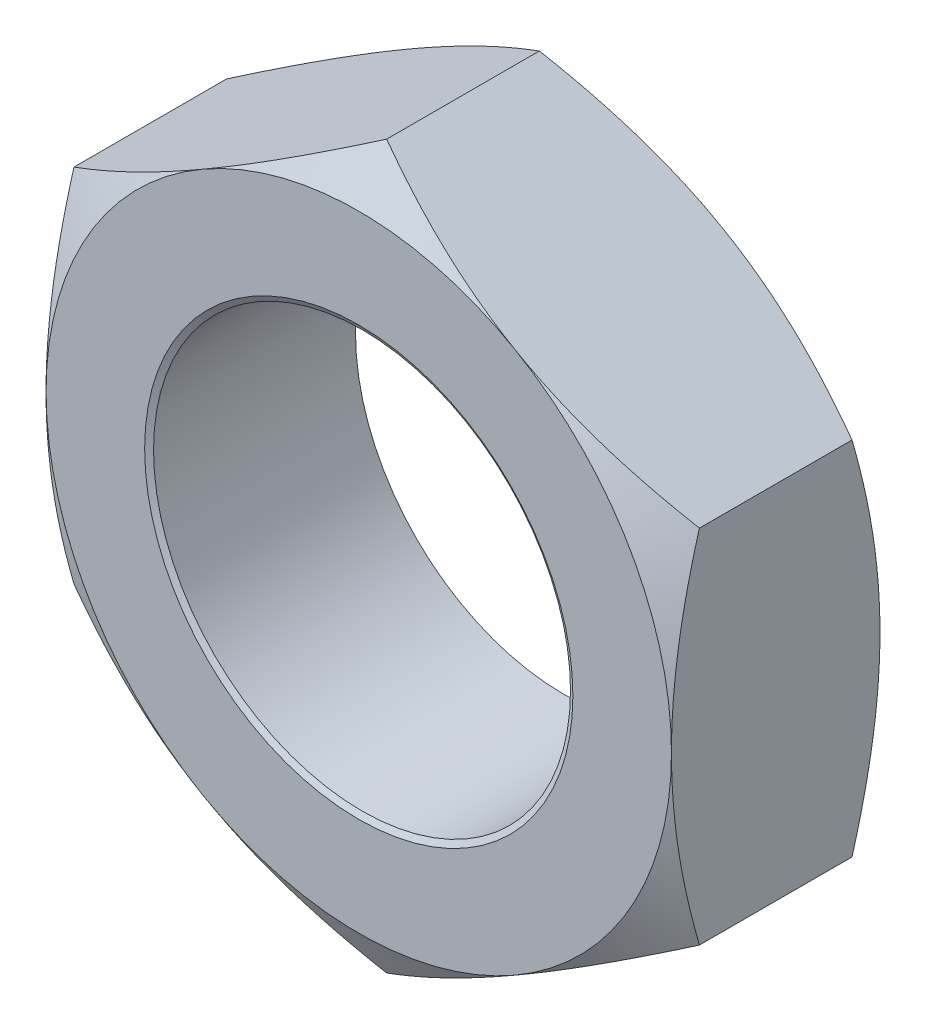
SolidWorks part; units mm, degrees
ref_plane "Front Plane" through (0, 0, 0) normal (0, 0, 1) x (1, 0, 0)
ref_plane "Top Plane" through (0, 0, 0) normal (0, 1, 0) x (1, 0, 0)
ref_plane "Right Plane" through (0, 0, 0) normal (1, 0, 0) x (0, 0, -1)
sketch "Sketch1" plane through (0, 0, 0) normal (0, 0, 1) x (1, 0, 0)
  line L1 (0, 13.8564) -> (-12, 6.9282)
  line L2 (-12, 6.9282) -> (-12, -6.9282)
  line L3 (-12, -6.9282) -> (0, -13.8564)
  line L4 (0, -13.8564) -> (12, -6.9282)
  line L5 (12, -6.9282) -> (12, 6.9282)
  line L6 (12, 6.9282) -> (0, 13.8564)
  circle A0 centre (0, 0) radius 12 construction
  circle A1 centre (0, 0) radius 8
  point P1 (0, 8)
  point P11 (8, 0)
  dimension "Thread Size" = 16
  dimension "HexWIdth" = 24
sketch "Sketch2" plane through (0, 0, 0) normal (1, 0, 0) x (0, 0, -1)
  line L0 (4, 0) -> (-4, 0) construction
  line L1 (-4, -8) -> (-4, 8) construction
  line L8 (-5.875, 8.2165) -> (-3.875, 8.2165) construction
  line L9 (-3.875, 8.2165) -> (-4.875, 6.4845) construction
  line L10 (-4.875, 6.4845) -> (-5.875, 8.2165) construction
  line L11 (-5.75, 8) -> (-4, 8) construction
  line L12 (-5, 6.701) -> (-4.75, 6.701) construction
  line L13 (-4.875, 6.4845) -> (-4.875, 6.701) construction
  line L14 (-4.875, 8) -> (-4.875, 8.2165) construction
  line L15 (-5.8125, 8.1083) -> (-3.9375, 8.1083)
  line L16 (-3.9375, 8.1083) -> (-4.75, 6.701)
  line L17 (-4.75, 6.701) -> (-5, 6.701)
  line L18 (-5, 6.701) -> (-5.8125, 8.1083)
  point P4 (0, 0)
  point P8 (-4, 0)
  point P23 (-4.875, 8.1083)
  dimension "Height" = 8
  dimension "Pitch" = 2
  dimension "D1" = 0.25
sketch "Sketch3" plane through (0, 0, 0) normal (0, 0, 1) x (1, 0, 0)
  line L0 (-12, 6.9282) -> (-12, -6.9282) construction
  line L1 (-12, -6.9282) -> (0, -13.8564) construction
  line L2 (0, -13.8564) -> (12, -6.9282) construction
  line L3 (12, -6.9282) -> (12, 6.9282) construction
  line L4 (12, 6.9282) -> (0, 13.8564) construction
  line L5 (0, 13.8564) -> (-12, 6.9282) construction
  line L6 (-12, 6.9282) -> (-12, -6.9282)
  line L7 (-12, -6.9282) -> (0, -13.8564)
  line L8 (0, -13.8564) -> (12, -6.9282)
  line L9 (12, -6.9282) -> (12, 6.9282)
  line L10 (12, 6.9282) -> (0, 13.8564)
  line L11 (0, 13.8564) -> (-12, 6.9282)
  circle A0 centre (0, 0) radius 8 construction
  circle A1 centre (0, 0) radius 8
extrude "Boss-Extrude1" add sketch "Sketch3" along normal mid plane 8
sketch "Sketch4" plane through (0, 0, 4) normal (0, 0, 1) x (1, 0, 0)
  circle A0 centre (0, 0) radius 12 construction
  circle A1 centre (0, 0) radius 12
  circle A2 centre (0, 0) radius 8.2165
extrude "Cut-Extrude1" cut sketch "Sketch4" against normal blind 10 draft 60 flip side to cut
mirror "Mirror1" about plane through (0, 0, 0) normal (0, 0, 1) of "Cut-Extrude1"
sketch "Sketch6" [suppressed] plane through (0, 0, 4) normal (0, 0, 1) x (1, 0, 0)
  circle A0 centre (0, 0) radius 8 construction
  circle A1 centre (0, 0) radius 8
ref_axis "Center Axis" through (0, 0, 3.875) along (0, 0, -1)
curve "Helix/Spiral1" [suppressed] pitch 2 height 10 turns 5
sketch "Sketch7" [suppressed] plane through (0, 0, 0) normal (1, 0, 0) x (0, 0, -1)
  line L0 (-5.8125, 8.1083) -> (-3.9375, 8.1083) construction
  line L1 (-3.9375, 8.1083) -> (-4.75, 6.701) construction
  line L2 (-4.75, 6.701) -> (-5, 6.701) construction
  line L3 (-5, 6.701) -> (-5.8125, 8.1083) construction
  line L4 (-5.8125, 8.1083) -> (-3.9375, 8.1083)
  line L5 (-3.9375, 8.1083) -> (-4.75, 6.701)
  line L6 (-4.75, 6.701) -> (-5, 6.701)
  line L7 (-5, 6.701) -> (-5.8125, 8.1083)
sweep "Sweep1" [suppressed] add profiles "Sketch7" path "Helix/Spiral1"
sketch "Sketch8" [suppressed] plane through (0, 0, 4) normal (0, 0, 1) x (1, 0, 0)
  circle A0 centre (0, 0) radius 8.2165 construction
  circle A1 centre (0, 0) radius 8.2165
extrude "Cut-Extrude2" [suppressed] cut sketch "Sketch8" against normal blind 10 draft 60 and the other way through all
mirror "Mirror2" [suppressed] about plane through (0, 0, 0) normal (0, 0, 1)
equation "\"D1@Sketch2\"=\"Pitch@Sketch2\"/8"
equation "\"D1@Boss-Extrude1\"=\"Height@Sketch2\""
equation "\"D4@Helix/Spiral1\"=\"Pitch@Sketch2\""
equation "\"D3@Helix/Spiral1\"=\"Height@Sketch2\"+\"D4@Helix/Spiral1\""
